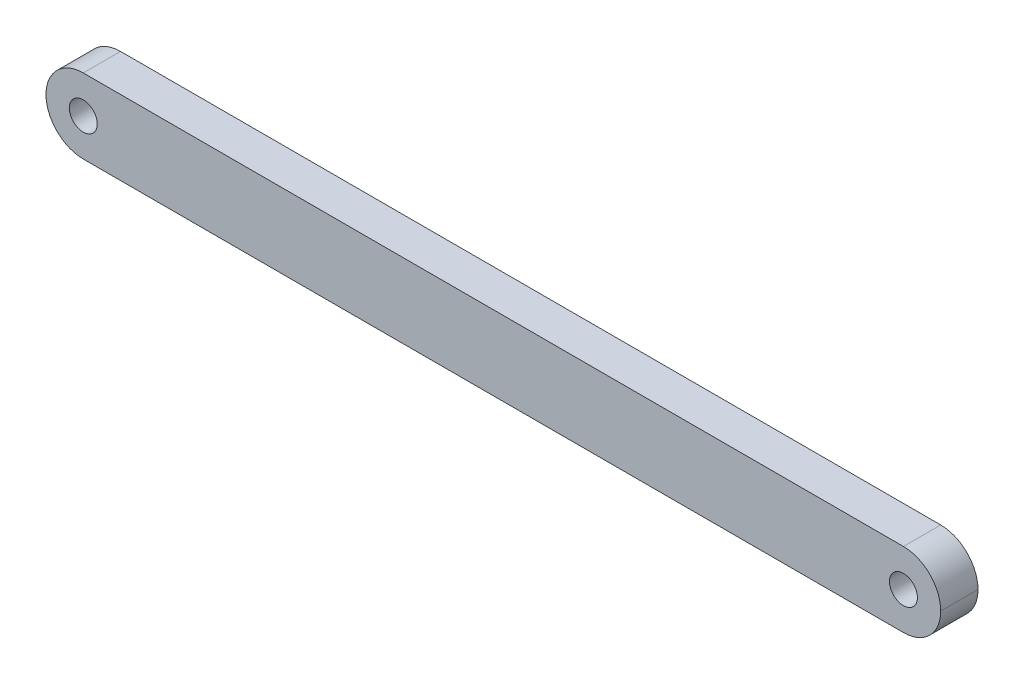
SolidWorks part; units mm, degrees
ref_plane "Front Plane" through (0, 0, 0) normal (0, 0, 1) x (1, 0, 0)
ref_plane "Top Plane" through (0, 0, 0) normal (0, 1, 0) x (1, 0, 0)
ref_plane "Right Plane" through (0, 0, 0) normal (1, 0, 0) x (0, 0, -1)
sketch "Sketch1" plane through (0, 0, 0) normal (0, 0, 1) x (1, 0, 0)
  line L1 (0, 0) -> (152.4, 0)
  line L2 (0, 0) -> (0, 12.7)
  line L3 (0, 12.7) -> (152.4, 12.7)
  line L4 (152.4, 0) -> (152.4, 12.7)
  dimension "D1" = 152.4
  dimension "D2" = 12.7
extrude "Boss-Extrude1" add sketch "Sketch1" along normal blind 6.35
fillet "Fillet1" radius 6.35 4 edges at (0, 0, 3.175) (0, 12.7, 3.175) (152.4, 0, 3.175) (152.4, 12.7, 3.175)
sketch "Sketch2" plane through (0, 0, 6.35) normal (0, 0, 1) x (1, 0, 0)
  line L0 (146.05, 12.7) -> (6.35, 12.7) construction
  circle A0 centre (6.35, 6.35) radius 2.3813
  circle A1 centre (146.05, 6.35) radius 2.3813
  dimension "D1" = 4.7625
  dimension "D3" = 139.7
  dimension "D2" = 6.35
  dimension "D4" = 6.35
  dimension "D5" = 6.35
extrude "Cut-Extrude1" cut sketch "Sketch2" against normal blind 25.4
